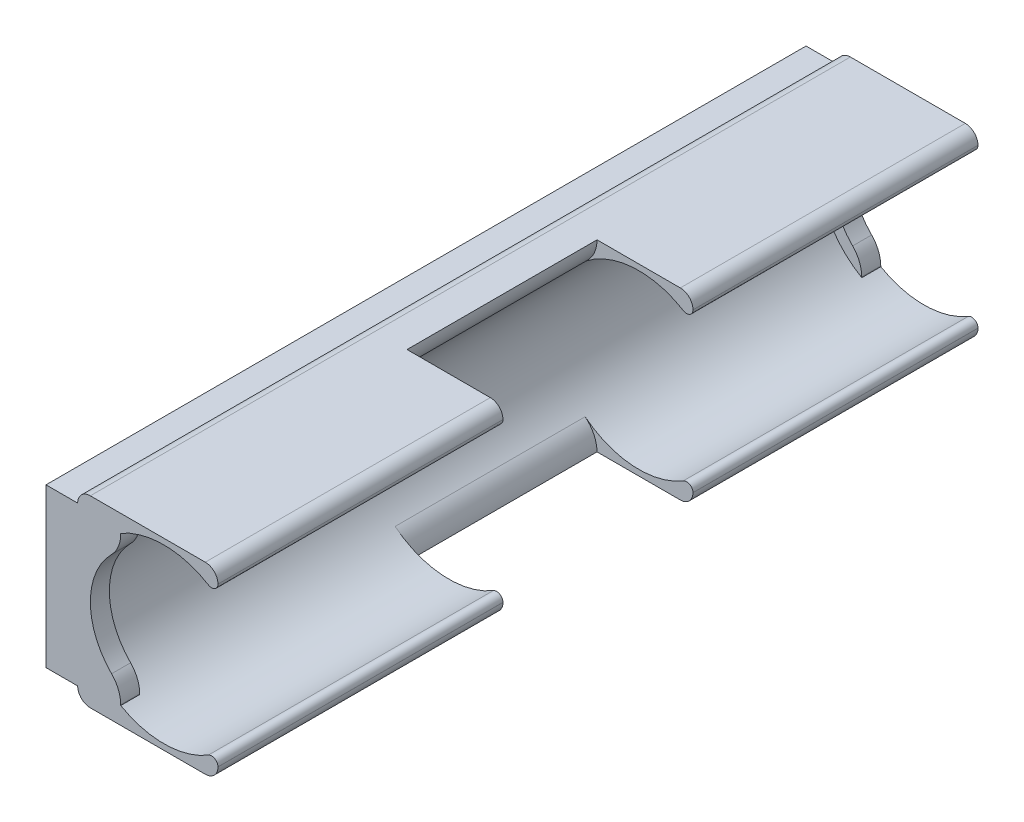
SolidWorks part; units mm, degrees
ref_plane "Front Plane" through (0, 0, 0) normal (0, 0, 1) x (1, 0, 0)
ref_plane "Top Plane" through (0, 0, 0) normal (0, 1, 0) x (1, 0, 0)
ref_plane "Right Plane" through (0, 0, 0) normal (1, 0, 0) x (0, 0, -1)
sketch "Sketch1" plane through (0, 0, 0) normal (1, 0, 0) x (0, 0, -1)
  line L1 (0, 0) -> (120, 0)
  line L2 (0, 0) -> (0, 25)
  line L3 (0, 25) -> (120, 25)
  line L4 (120, 0) -> (120, 25)
  dimension "D1" = 25
  dimension "D2" = 120
extrude "Base" add sketch "Sketch1" along normal blind 5
sketch "Sketch2" plane through (0, 0, 0) normal (0, 0, 1) x (1, 0, 0)
  line L0 (5, 25) -> (5, 0) construction
  line L1 (5, 25) -> (5, 0) construction
  line L2 (5, 12.5) -> (32.2, 12.5) construction
  line L5 (7, 27) -> (25.151, 27)
  line L6 (27.151, 23.0755) -> (27.151, 25)
  line L7 (7, -2) -> (25.151, -2)
  line L8 (27.151, 1.9245) -> (27.151, 0)
  line L9 (5, 0) -> (5, 25)
  circle A0 centre (18.6, 12.5) radius 13.6
  arc A1 (5, 25) -> (7, 27) centre (7, 25) cw
  arc A2 (25.151, 27) -> (27.151, 25) centre (25.151, 25) cw
  arc A3 (5, 0) -> (7, -2) centre (7, 0) ccw
  arc A4 (25.151, -2) -> (27.151, 0) centre (25.151, 0) ccw
  point P2 (5, 12.5)
  point P15 (7, 25)
  point P18 (27.151, 27)
  line M8 (5, 0) -> (5, 25)
  dimension "D1" = 27.2
  dimension "D4" = 2
  dimension "D5" = 2
  dimension "D2" = 20.25
  dimension "D3" = 2
extrude "Clip" add sketch "Sketch2" against normal up to surface (120 mm away) contours A2 L5 A1 A0 L6 M8 | L7 A4 L8 A0 A3 M8 region at (16.0755, 26.7353, 0) region at (12.6265, -0.0119, 0) up to face at (2.5, 12.5, -120)
sketch3d "3DSketch1"
  line L0 (0, 25, -120) -> (0, 25, 0) construction
  line L1 (0, 0, 0) -> (0, 0, -120) construction
  point P0 (0, 25, -60)
  point P1 (0, 0, -60)
ref_plane "Plane2" through (0, 0, -60) normal (0, 0, -1) x (-1, 0, 0)
sketch "Sketch3" plane through (0, 0, 0) normal (-1, 0, 0) x (0, 0, 1)
  line L0 (-120, 0) -> (-120, 25) construction
  line L2 (-60, 13.75) -> (-60, -13.75) construction
  circle A0 centre (-100, 12.5) radius 1.5
  circle A2 centre (-100, 12.5) radius 3
  circle A3 centre (-20, 12.5) radius 3
  circle A4 centre (-20, 12.5) radius 1.5
  point P4 (-120, 12.5)
  dimension "D1" = 3
  dimension "D3" = 6
  dimension "D2" = 20
extrude "ScrewHoles" cut sketch "Sketch3" against normal blind 10 contours A4 | A0
sketch "Sketch4" plane through (0, 0, 0) normal (0, 0, 1) x (1, 0, 0)
  line L2 (18.6, 12.5) -> (5, 12.5)
  line L4 (11.8, 0.7221) -> (11.8, 0.8244)
  line L6 (11.8, 24.1756) -> (11.8, 24.2779)
  arc A1 (10.3542, 20.6589) -> (10.3542, 4.3411) centre (18.6, 12.5) ccw
  arc A2 (27.151, 23.0755) -> (27.151, 1.9245) centre (18.6, 12.5) ccw construction
  arc A3 (11.8, 24.2779) -> (11.8, 0.7221) centre (18.6, 12.5) ccw
  arc A4 (10.3542, 4.3411) -> (11.8, 0.8244) centre (6.8, 0.8244) cw
  arc A5 (10.3542, 20.6589) -> (11.8, 24.1756) centre (6.8, 24.1756) ccw
  point P11 (11.8, 12.5)
  point P15 (5, 12.5)
  point P18 (18.6, 12.5)
  point P20 (11.8, 3.1021)
  point P23 (11.8, 21.8979)
  dimension "D1" = 2
  dimension "D2" = 5
extrude "ClipWall" add sketch "Sketch4" against normal blind 3 contours A1 A4 L4 A3 L6 A5
mirror "Mirror1" about plane through (0, 0, -60) normal (0, 0, -1) of "ClipWall"
fillet "RoundedCorners" radius 1 2 edges at (27.151, 1.9245, -60) (27.151, 23.0755, -60)
sketch "Sketch5" plane through (0, 0, -60) normal (0, 0, -1) x (-1, 0, 0)
  line L1 (-27.151, 27) -> (-12, 27)
  line L2 (-27.151, 27) -> (-27.151, -2)
  line L3 (-27.151, -2) -> (-12, -2)
  line L4 (-12, 27) -> (-12, -2)
  line L6 (-25.151, -2) -> (-7, -2) construction
  line L7 (-25.151, 27) -> (-7, 27) construction
  dimension "D1" = 5
extrude "FingerGap" cut sketch "Sketch5" against normal mid plane 30
fillet "FingerGroove" radius 5 2 edges at (12, 0.6088, -60) (12, 24.3912, -60)
extrude "Cut-Extrude1" cut sketch "Sketch3<3>" along normal blind 5 from offset 7 offset against normal yes
sketch "Sketch3<3>" plane through (0, 0, 0) normal (-1, 0, 0) x (0, 0, 1) same geometry as "Sketch3"
